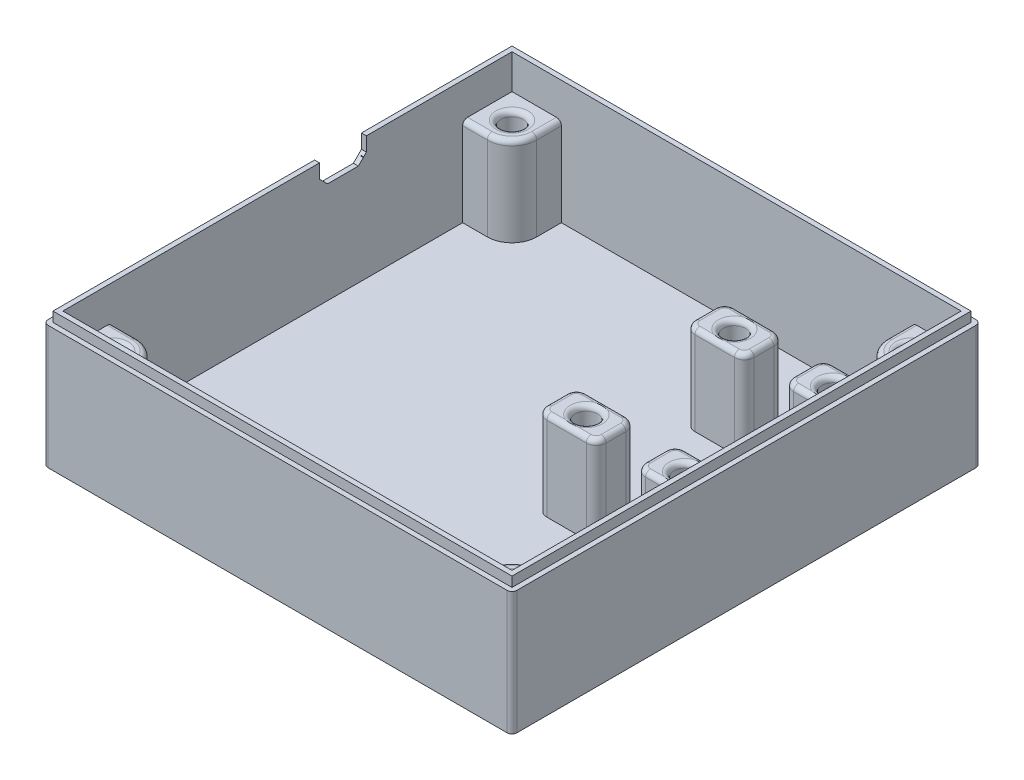
SolidWorks part; units mm, degrees
ref_plane "Front Plane" through (0, 0, 0) normal (0, 0, 1) x (1, 0, 0)
ref_plane "Top Plane" through (0, 0, 0) normal (0, 1, 0) x (1, 0, 0)
ref_plane "Right Plane" through (0, 0, 0) normal (1, 0, 0) x (0, 0, -1)
sketch "Sketch1" plane through (0, 0, 0) normal (0, 1, 0) x (1, 0, 0)
  line L1 (-47.5, -47.5) -> (47.5, -47.5)
  line L2 (-47.5, -47.5) -> (-47.5, 47.5)
  line L3 (-47.5, 47.5) -> (47.5, 47.5)
  line L4 (47.5, -47.5) -> (47.5, 47.5)
  line L5 (-47.5, -47.5) -> (47.5, 47.5) construction
  line L6 (-47.5, 47.5) -> (47.5, -47.5) construction
  point P0 (0, 0)
  dimension "D1" = 95
  dimension "D2" = 95
extrude "Boss-Extrude1" add sketch "Sketch1" along normal blind 2
sketch "Sketch2" plane through (0, 2, 0) normal (0, 1, 0) x (1, 0, 0)
  line L4 (47.5, -47.5) -> (47.5, 47.5)
  line L5 (47.5, 47.5) -> (-47.5, 47.5)
  line L6 (-47.5, 47.5) -> (-47.5, -47.5)
  line L7 (-47.5, -47.5) -> (47.5, -47.5)
  line L8 (47.5, -47.5) -> (47.5, 47.5)
  line L9 (47.5, 47.5) -> (-47.5, 47.5)
  line L10 (-47.5, 47.5) -> (-47.5, -47.5)
  line L11 (-47.5, -47.5) -> (47.5, -47.5)
  line L16 (45.5, -45.5) -> (45.5, 45.5)
  line L17 (45.5, 45.5) -> (-45.5, 45.5)
  line L18 (-45.5, 45.5) -> (-45.5, -45.5)
  line L19 (-45.5, -45.5) -> (45.5, -45.5)
  line L20 (45.5, -45.5) -> (45.5, 45.5)
  line L21 (45.5, 45.5) -> (-45.5, 45.5)
  line L22 (-45.5, 45.5) -> (-45.5, -45.5)
  line L23 (-45.5, -45.5) -> (45.5, -45.5)
  dimension "D1" = 0
  dimension "D2" = 2
extrude "Boss-Extrude2" add sketch "Sketch2" along normal blind 25
sketch "Sketch3" plane through (0, 2, 0) normal (0, 1, 0) x (1, 0, 0)
  line L1 (-45.5, 45.5) -> (-35.5, 45.5)
  line L2 (-45.5, 45.5) -> (-45.5, 35.5)
  line L3 (-45.5, 35.5) -> (-40.5, 35.5)
  line L4 (-35.5, 45.5) -> (-35.5, 40.5)
  line L43 (0, 0) -> (8.4547, 0) construction
  line L44 (0, 0) -> (0, 12.2196) construction
  line L45 (35.5, 45.5) -> (35.5, 40.5)
  line L46 (45.5, 35.5) -> (40.5, 35.5)
  line L47 (45.5, 45.5) -> (45.5, 35.5)
  line L48 (45.5, 45.5) -> (35.5, 45.5)
  line L49 (45.5, -45.5) -> (35.5, -45.5)
  line L50 (45.5, -45.5) -> (45.5, -35.5)
  line L51 (45.5, -35.5) -> (40.5, -35.5)
  line L52 (35.5, -45.5) -> (35.5, -40.5)
  line L53 (-35.5, -45.5) -> (-35.5, -40.5)
  line L54 (-45.5, -35.5) -> (-40.5, -35.5)
  line L55 (-45.5, -45.5) -> (-45.5, -35.5)
  line L56 (-45.5, -45.5) -> (-35.5, -45.5)
  arc A0 (-40.5, 35.5) -> (-35.5, 40.5) centre (-40.5, 40.5) ccw
  arc A10 (40.5, 35.5) -> (35.5, 40.5) centre (40.5, 40.5) cw
  arc A11 (40.5, -35.5) -> (35.5, -40.5) centre (40.5, -40.5) ccw
  arc A12 (-40.5, -35.5) -> (-35.5, -40.5) centre (-40.5, -40.5) cw
  point P7 (-35.5, 35.5)
  point P19 (35.5, 35.5)
  point P33 (35.5, -35.5)
  point P34 (-35.5, -35.5)
  dimension "D3" = 5
  dimension "D1" = 10
  dimension "D2" = 10
extrude "Boss-Extrude3" add sketch "Sketch3" along normal blind 18
sketch "Sketch4" plane through (0, 20, 0) normal (0, 1, 0) x (1, 0, 0)
  line L0 (-45.5, 0) -> (45.5, 0) construction
  line L1 (-45.5, 45.5) -> (-45.5, -45.5) construction
  line L2 (45.5, -35.5) -> (45.5, 35.5) construction
  line L4 (-45.5, 45.5) -> (-45.5, 35.5)
  line L5 (-45.5, 35.5) -> (-40.5, 35.5)
  line L6 (-35.5, 40.5) -> (-35.5, 45.5)
  line L7 (-35.5, 45.5) -> (-45.5, 45.5)
  line L8 (-45.5, 45.5) -> (-45.5, 35.5) construction
  line L9 (-45.5, 35.5) -> (-40.5, 35.5) construction
  line L10 (-35.5, 40.5) -> (-35.5, 45.5) construction
  line L11 (-35.5, 45.5) -> (-45.5, 45.5) construction
  line L24 (0, 45.5) -> (0, -45.5) construction
  line L25 (45.5, 45.5) -> (-45.5, 45.5) construction
  line L26 (-45.5, -45.5) -> (45.5, -45.5) construction
  line L27 (35.5, 45.5) -> (45.5, 45.5) construction
  line L28 (35.5, 40.5) -> (35.5, 45.5) construction
  line L29 (45.5, 35.5) -> (40.5, 35.5) construction
  line L30 (45.5, 45.5) -> (45.5, 35.5) construction
  line L31 (45.5, -45.5) -> (45.5, -35.5) construction
  line L32 (45.5, -35.5) -> (40.5, -35.5) construction
  line L33 (35.5, -40.5) -> (35.5, -45.5) construction
  line L34 (35.5, -45.5) -> (45.5, -45.5) construction
  line L35 (-35.5, -45.5) -> (-45.5, -45.5) construction
  line L36 (-35.5, -40.5) -> (-35.5, -45.5) construction
  line L37 (-45.5, -35.5) -> (-40.5, -35.5) construction
  line L38 (-45.5, -45.5) -> (-45.5, -35.5) construction
  circle A0 centre (-40.5, 40.5) radius 2.25
  arc A1 (-40.5, 35.5) -> (-35.5, 40.5) centre (-40.5, 40.5) ccw
  arc A2 (-40.5, 35.5) -> (-35.5, 40.5) centre (-40.5, 40.5) ccw construction
  arc A29 (40.5, 35.5) -> (35.5, 40.5) centre (40.5, 40.5) cw construction
  circle A30 centre (40.5, 40.5) radius 2.25
  arc A31 (40.5, -35.5) -> (35.5, -40.5) centre (40.5, -40.5) ccw construction
  arc A32 (-40.5, -35.5) -> (-35.5, -40.5) centre (-40.5, -40.5) cw construction
  circle A33 centre (40.5, -40.5) radius 2.25
  circle A34 centre (-40.5, -40.5) radius 2.25
  dimension "D2" = 4.5
  dimension "D1" = 0
extrude "Cut-Extrude1" cut sketch "Sketch4" against normal up to surface (18 mm away) up to face at (0, 2, 0)
sketch "Sketch6" plane through (0, 2, 0) normal (0, 1, 0) x (1, 0, 0)
  line L0 (45.5, -35.5) -> (45.5, 35.5) construction
  line L1 (14.69, 30.37) -> (22.69, 30.37)
  line L3 (14.69, 22.37) -> (22.69, 22.37)
  line L4 (45.5, 30.37) -> (45.5, 22.37)
  line L5 (24.69, 28.37) -> (24.69, 24.37)
  line L6 (32.69, 28.37) -> (32.69, 24.37)
  line L7 (14.69, 0.37) -> (22.69, 0.37)
  line L9 (14.69, -7.63) -> (22.69, -7.63)
  line L10 (45.5, 0.37) -> (45.5, -7.63)
  line L11 (34.69, 22.37) -> (45.5, 22.37)
  line L12 (34.69, 30.37) -> (45.5, 30.37)
  line L13 (24.69, -1.63) -> (24.69, -5.63)
  line L14 (35.5, 45.5) -> (-35.5, 45.5) construction
  line L15 (12.69, 28.37) -> (12.69, 24.37)
  line L16 (12.69, -1.63) -> (12.69, -5.63)
  line L17 (32.69, -1.63) -> (32.69, -5.63)
  line L18 (34.69, -7.63) -> (45.5, -7.63)
  line L19 (34.69, 0.37) -> (45.5, 0.37)
  circle A0 centre (38.69, 26.37) radius 2.25
  circle A1 centre (38.69, -3.63) radius 2.25
  circle A2 centre (18.69, 26.37) radius 2.25
  circle A3 centre (18.69, -3.63) radius 2.25
  arc A4 (12.69, -5.63) -> (14.69, -7.63) centre (14.69, -5.63) ccw
  arc A5 (12.69, -1.63) -> (14.69, 0.37) centre (14.69, -1.63) cw
  arc A6 (12.69, 24.37) -> (14.69, 22.37) centre (14.69, 24.37) ccw
  arc A7 (12.69, 28.37) -> (14.69, 30.37) centre (14.69, 28.37) cw
  arc A8 (24.69, 28.37) -> (22.69, 30.37) centre (22.69, 28.37) ccw
  arc A9 (24.69, 24.37) -> (22.69, 22.37) centre (22.69, 24.37) cw
  arc A10 (32.69, 24.37) -> (34.69, 22.37) centre (34.69, 24.37) ccw
  arc A11 (32.69, 28.37) -> (34.69, 30.37) centre (34.69, 28.37) cw
  arc A12 (24.69, -5.63) -> (22.69, -7.63) centre (22.69, -5.63) cw
  arc A13 (32.69, -5.63) -> (34.69, -7.63) centre (34.69, -5.63) ccw
  arc A14 (32.69, -1.63) -> (34.69, 0.37) centre (34.69, -1.63) cw
  arc A15 (24.69, -1.63) -> (22.69, 0.37) centre (22.69, -1.63) ccw
  point P10 (45.5, 26.37)
  point P19 (45.5, -3.63)
  point P40 (32.69, 22.37)
  point P43 (32.69, 30.37)
  point P52 (32.69, -7.63)
  point P55 (32.69, 0.37)
  dimension "D2" = 4.5
  dimension "D3" = 6.81
  dimension "D8" = 2
  dimension "D11" = 2
  dimension "D13" = 2
  dimension "D1" = 8
  dimension "D4" = 19.13
  dimension "D5" = 20
  dimension "D6" = 30
  dimension "D7" = 6
  dimension "D9" = 6
  dimension "D10" = 6
  dimension "D12" = 6
extrude "Boss-Extrude4" add sketch "Sketch6" along normal up to surface (18 mm away) up to face at (40.5, 20, -42.75)
fillet "Fillet1" radius 1 18 edges at (13.2758, 20, 0.2158) (18.69, 20, -0.37) (18.69, 20, 7.63) (13.2758, 20, 7.0442) (12.69, 20, 3.63) (18.69, 20, 1.38) (13.2758, 20, -22.9558) (12.69, 20, -26.37) (13.2758, 20, -29.7842) (18.69, 20, -30.37) (18.69, 20, -22.37) (18.69, 20, -28.62) (24.1042, 20, 0.2158) (24.69, 20, 3.63) (24.1042, 20, 7.0442) (24.1042, 20, -29.7842) (24.69, 20, -26.37) (24.1042, 20, -22.9558)
fillet "Fillet2" radius 1 16 edges at (-43, 20, -35.5) (-35.5, 20, -43) (-40.5, 20, -38.25) (-36.9645, 20, -36.9645) (-35.5, 20, 43) (-43, 20, 35.5) (43, 20, 35.5) (35.5, 20, 43) (35.5, 20, -43) (43, 20, -35.5) (-36.9645, 20, 36.9645) (36.9645, 20, 36.9645) (36.9645, 20, -36.9645) (-40.5, 20, 38.25) (40.5, 20, 42.75) (40.5, 20, -42.75)
sketch "Sketch7" plane through (-47.5, 0, 0) normal (-1, 0, 0) x (0, 0, 1)
  line L0 (-15, 27) -> (-15, 24.55)
  line L1 (-47.5, 27) -> (47.5, 27) construction
  line L2 (-15, 24.55) -> (-13.95, 23.5)
  line L3 (-13.95, 23.5) -> (-8.55, 23.5)
  line L4 (-8.55, 23.5) -> (-7.5, 24.55)
  line L5 (-7.5, 24.55) -> (-7.5, 27)
  line L6 (-15, 27) -> (-7.5, 27)
  line L7 (-47.5, 27) -> (-47.5, 0) construction
  dimension "D1" = 7.5
  dimension "D2" = 32.5
  dimension "D3" = 135
  dimension "D4" = 135
  dimension "D5" = 5.4
  dimension "D6" = 3.5
extrude "Cut-Extrude2" cut sketch "Sketch7" against normal up to next
sketch "Sketch8" plane through (0, 27, 0) normal (0, 1, 0) x (1, 0, 0)
  line L1 (-45.5, 8.55) -> (-46, 8.55)
  line L2 (-45.5, 8.55) -> (-45.5, 7.05)
  line L3 (-45.5, 7.05) -> (-46, 7.05)
  line L4 (-46, 8.55) -> (-46, 7.05)
  line L5 (-45.5, 13.95) -> (-46, 13.95)
  line L6 (-45.5, 13.95) -> (-45.5, 15.45)
  line L7 (-45.5, 15.45) -> (-46, 15.45)
  line L8 (-46, 13.95) -> (-46, 15.45)
  dimension "D1" = 1.5
  dimension "D2" = 0.5
  dimension "D3" = 1.5
  dimension "D4" = 0.5
extrude "Cut-Extrude3" cut sketch "Sketch8" against normal up to surface (3.5 mm away) up to face at (-46.5, 23.5, -11.25)
sketch "Sketch9" plane through (-47.5, 0, 0) normal (-1, 0, 0) x (0, 0, 1)
  line L5 (-7.5, 24.55) -> (-7.5, 27) construction
  line L6 (-8.55, 23.5) -> (-7.5, 24.55) construction
  line L7 (-13.95, 23.5) -> (-8.55, 23.5) construction
  line L8 (-15, 27) -> (-15, 24.55) construction
  line L9 (-15, 24.55) -> (-13.95, 23.5) construction
  line L10 (-6.5, 24.1358) -> (-6.5, 27)
  line L11 (-8.1358, 22.5) -> (-6.5, 24.1358)
  line L12 (-14.3642, 22.5) -> (-8.1358, 22.5)
  line L13 (-16, 24.1358) -> (-14.3642, 22.5)
  line L14 (-16, 27) -> (-16, 24.1358)
  line L15 (-6.5, 24.1358) -> (-6.5, 27)
  line L16 (-8.1358, 22.5) -> (-6.5, 24.1358)
  line L17 (-14.3642, 22.5) -> (-8.1358, 22.5)
  line L18 (-16, 24.1358) -> (-14.3642, 22.5)
  line L19 (-16, 27) -> (-16, 24.1358)
  line L20 (-7.5, 24.55) -> (-7.5, 27)
  line L21 (-8.55, 23.5) -> (-7.5, 24.55)
  line L22 (-13.95, 23.5) -> (-8.55, 23.5)
  line L23 (-15, 27) -> (-15, 24.55)
  line L24 (-15, 24.55) -> (-13.95, 23.5)
  line L25 (-16, 27) -> (-15, 27)
  line L26 (-7.5, 27) -> (-6.5, 27)
  dimension "D1" = 1
extrude "Cut-Extrude4" cut sketch "Sketch9" against normal blind 0.8
fillet "Fillet3" radius 1 2 edges at (47.5, 13.5, 47.5) (-47.5, 13.5, -47.5)
fillet "Fillet4" radius 1 2 edges at (47.5, 13.5, -47.5) (-47.5, 13.5, 47.5)
sketch "Sketch11" plane through (0, 27, 0) normal (0, 1, 0) x (1, 0, 0)
  line L0 (47.5, -46.5) -> (47.5, 46.5) construction
  line L1 (-46.5, 47.5) -> (46.5, 47.5)
  line L2 (-47.5, 46.5) -> (-47.5, -46.5)
  line L3 (-46.5, -47.5) -> (46.5, -47.5)
  line L4 (47.5, 46.5) -> (47.5, -46.5)
  line L5 (-46.5, -47.5) -> (46.5, -47.5) construction
  line L6 (-47.5, 46.5) -> (-47.5, 16) construction
  line L7 (46.5, 47.5) -> (-46.5, 47.5) construction
  line L8 (-46.5, 46.5) -> (46.5, 46.5)
  line L9 (46.5, 46.5) -> (46.5, -46.5)
  line L10 (-46.5, -46.5) -> (46.5, -46.5)
  line L11 (-46.5, 46.5) -> (-46.5, -46.5)
  arc A0 (46.5, -47.5) -> (47.5, -46.5) centre (46.5, -46.5) ccw
  arc A1 (-46.5, 47.5) -> (-47.5, 46.5) centre (-46.5, 46.5) ccw
  arc A2 (46.5, 47.5) -> (47.5, 46.5) centre (46.5, 46.5) cw
  arc A3 (-47.5, -46.5) -> (-46.5, -47.5) centre (-46.5, -46.5) ccw
  arc A4 (46.5, 46.5) -> (46.5, 46.5) centre (46.5, 46.5) cw
  arc A5 (46.5, -46.5) -> (46.5, -46.5) centre (46.5, -46.5) ccw
  arc A6 (-46.5, -46.5) -> (-46.5, -46.5) centre (-46.5, -46.5) ccw
  arc A7 (-46.5, 46.5) -> (-46.5, 46.5) centre (-46.5, 46.5) ccw
  dimension "D1" = 1
  dimension "D2" = 1
  dimension "D3" = 1
extrude "Cut-Extrude6" cut sketch "Sketch11" against normal blind 2
sketch "Sketch12" plane through (-46.7, 0, 0) normal (-1, 0, 0) x (0, 0, 1)
  line L12 (-7.5, 24.55) -> (-8.55, 23.5)
  line L13 (-8.55, 23.5) -> (-13.95, 23.5)
  line L14 (-13.95, 23.5) -> (-15, 24.55)
  line L15 (-15, 24.55) -> (-15, 25)
  line L16 (-15, 25) -> (-16, 25)
  line L17 (-16, 25) -> (-16, 24.1358)
  line L18 (-16, 24.1358) -> (-14.3642, 22.5)
  line L19 (-14.3642, 22.5) -> (-8.1358, 22.5)
  line L20 (-8.1358, 22.5) -> (-6.5, 24.1358)
  line L21 (-6.5, 24.1358) -> (-6.5, 25)
  line L22 (-15, 25) -> (-16, 25)
  line L23 (-7.5, 25) -> (-7.5, 24.55)
  line L24 (-7.5, 24.55) -> (-8.55, 23.5)
  line L25 (-8.55, 23.5) -> (-13.95, 23.5)
  line L26 (-13.95, 23.5) -> (-15, 24.55)
  line L27 (-15, 24.55) -> (-15, 25)
  line L29 (-16, 25) -> (-16, 24.1358)
  line L30 (-16, 24.1358) -> (-14.3642, 22.5)
  line L31 (-14.3642, 22.5) -> (-8.1358, 22.5)
  line L32 (-8.1358, 22.5) -> (-6.5, 24.1358)
  line L33 (-6.5, 24.1358) -> (-6.5, 25)
  line L35 (-7.5, 25) -> (-7.5, 24.55)
  line L36 (-6.5, 25) -> (-7.5, 25)
  line L37 (-6.5, 25) -> (-7.5, 25)
  dimension "D1" = 0
extrude "Cut-Extrude7" cut sketch "Sketch12" against normal up to next
sketch "Sketch13" plane through (0, 25, 0) normal (0, -1, 0) x (1, 0, 0)
  line L6 (-46.5, -15) -> (-46.5, -16)
  line L7 (-46.5, -16) -> (-45.5, -16)
  line L8 (-45.5, -16) -> (-45.5, -15.45)
  line L9 (-45.5, -15.45) -> (-46, -15.45)
  line L10 (-46, -15.45) -> (-46, -15)
  line L11 (-46, -15) -> (-46.5, -15)
  line L12 (-46.5, -15) -> (-46.5, -16)
  line L13 (-46.5, -16) -> (-45.5, -16)
  line L14 (-45.5, -16) -> (-45.5, -15.45)
  line L15 (-45.5, -15.45) -> (-46, -15.45)
  line L16 (-46, -15.45) -> (-46, -15)
  line L17 (-46, -15) -> (-46.5, -15)
  line L18 (-46.5, -6.5) -> (-46.5, -7.5)
  line L19 (-46.5, -7.5) -> (-46, -7.5)
  line L20 (-46, -7.5) -> (-46, -7.05)
  line L21 (-46, -7.05) -> (-45.5, -7.05)
  line L22 (-45.5, -7.05) -> (-45.5, -6.5)
  line L23 (-45.5, -6.5) -> (-46.5, -6.5)
  line L24 (-46.5, -6.5) -> (-46.5, -7.5)
  line L25 (-46.5, -7.5) -> (-46, -7.5)
  line L26 (-46, -7.5) -> (-46, -7.05)
  line L27 (-46, -7.05) -> (-45.5, -7.05)
  line L28 (-45.5, -7.05) -> (-45.5, -6.5)
  line L29 (-45.5, -6.5) -> (-46.5, -6.5)
  dimension "D1" = 0
  dimension "D2" = 0
extrude "Cut-Extrude8" cut sketch "Sketch13" against normal up to next
sketch "Sketch16" plane through (-47.5, 0, 0) normal (-1, 0, 0) x (0, 0, 1)
  line L0 (-6.5, 24.1358) -> (-6.5, 25) construction
  line L1 (-8.1358, 22.5) -> (-6.5, 24.1358) construction
  line L2 (-14.3642, 22.5) -> (-8.1358, 22.5) construction
  line L3 (-16, 24.1358) -> (-14.3642, 22.5) construction
  line L4 (-16, 25) -> (-16, 24.1358) construction
  line L5 (-6.5, 24.1358) -> (-6.5, 25)
  line L6 (-8.1358, 22.5) -> (-6.5, 24.1358)
  line L7 (-14.3642, 22.5) -> (-8.1358, 22.5)
  line L8 (-16, 24.1358) -> (-14.3642, 22.5)
  line L9 (-16, 25) -> (-16, 24.1358)
  line L10 (-18, 25) -> (-18, 23.3074)
  line L11 (-18, 23.3074) -> (-15.1926, 20.5)
  line L12 (-15.1926, 20.5) -> (-7.3074, 20.5)
  line L13 (-7.3074, 20.5) -> (-4.5, 23.3074)
  line L14 (-4.5, 23.3074) -> (-4.5, 25)
  line L15 (-18, 25) -> (-16, 25)
  line L16 (-6.5, 25) -> (-4.5, 25)
  dimension "D1" = 2
extrude "Cut-Extrude9" cut sketch "Sketch16" against normal up to surface (1 mm away) up to face at (-46.5, 26, 20)
fillet "Fillet5" radius 1 13 edges at (40.095, 20, 7.63) (33.2758, 20, 7.0442) (32.69, 20, 3.63) (40.095, 20, -0.37) (40.095, 20, -22.37) (40.095, 20, -30.37) (33.2758, 20, -29.7842) (32.69, 20, -26.37) (38.69, 2, -24.12) (38.69, 20, -28.62) (33.2758, 20, 0.2158) (38.69, 20, 1.38) (33.2758, 20, -22.9558)
